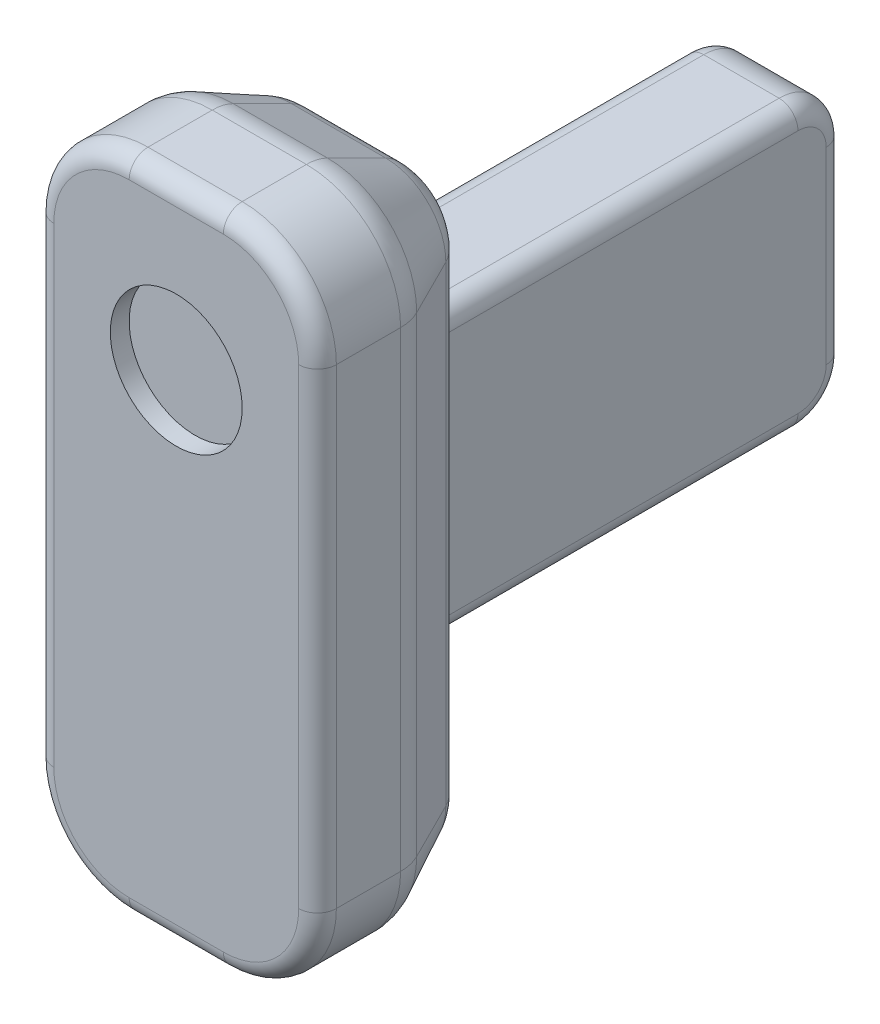
SolidWorks part; units mm, degrees
ref_plane "Front Plane" through (0, 0, 0) normal (0, 0, 1) x (1, 0, 0)
ref_plane "Top Plane" through (0, 0, 0) normal (0, 1, 0) x (1, 0, 0)
ref_plane "Right Plane" through (0, 0, 0) normal (1, 0, 0) x (0, 0, -1)
sketch "Sketch1" plane through (0, 0, 0) normal (0, 0, 1) x (1, 0, 0)
  line L1 (42.3673, -46.3138) -> (72.3673, -46.3138)
  line L2 (42.3673, -46.3138) -> (42.3673, -116.3138)
  line L3 (42.3673, -116.3138) -> (72.3673, -116.3138)
  line L4 (72.3673, -46.3138) -> (72.3673, -116.3138)
  dimension "D1" = 30
  dimension "D2" = 70
extrude "Boss-Extrude1" add sketch "Sketch1" against normal blind 20
fillet "Fillet1" radius 10 4 edges at (42.3673, -46.3138, -10) (72.3673, -46.3138, -10) (42.3673, -116.3138, -10) (72.3673, -116.3138, -10)
fillet "Fillet2" radius 2 8 edges at (69.4383, -113.3848, 0) (57.3673, -116.3138, 0) (45.2962, -113.3848, 0) (42.3673, -81.3138, 0) (45.2962, -49.2427, 0) (57.3673, -46.3138, 0) (69.4383, -49.2427, 0) (72.3673, -81.3138, 0)
chamfer "Chamfer1" distance 5 distance2 10 8 edges at (42.3673, -81.3138, -20) (45.2962, -113.3848, -20) (45.2962, -49.2427, -20) (57.3673, -116.3138, -20) (57.3673, -46.3138, -20) (69.4383, -113.3848, -20) (69.4383, -49.2427, -20) (72.3673, -81.3138, -20) first distance on face at (57.3673, -81.3138, -20)
fillet "Fillet3" radius 5 16 edges at (65.9028, -52.7782, -20) (57.3673, -51.3138, -20) (48.8317, -52.7782, -20) (47.3673, -81.3138, -20) (48.8317, -109.8493, -20) (57.3673, -111.3138, -20) (65.9028, -109.8493, -20) (69.4383, -113.3848, -10) (57.3673, -116.3138, -10) (45.2962, -113.3848, -10) (42.3673, -81.3138, -10) (45.2962, -49.2427, -10) (57.3673, -46.3138, -10) (69.4383, -49.2427, -10) (67.3673, -81.3138, -20) (72.3673, -81.3138, -10)
sketch "Sketch2" plane through (0, 0, -20) normal (0, 0, -1) x (-1, 0, 0)
  line L0 (-64.2771, -81.3138) -> (-50.4574, -81.3138) construction
  line L1 (-64.2771, -56.3138) -> (-64.2771, -106.3138) construction
  line L2 (-50.4574, -106.3138) -> (-50.4574, -56.3138) construction
  line L3 (-57.3673, -108.2236) -> (-57.3673, -54.4039) construction
  line L4 (-62.3673, -108.2236) -> (-52.3673, -108.2236) construction
  line L5 (-52.3673, -54.4039) -> (-62.3673, -54.4039) construction
  line L7 (-63.3673, -96.3138) -> (-51.3673, -96.3138)
  line L8 (-63.3673, -96.3138) -> (-63.3673, -66.3138)
  line L9 (-63.3673, -66.3138) -> (-51.3673, -66.3138)
  line L10 (-51.3673, -96.3138) -> (-51.3673, -66.3138)
  dimension "D1" = 12
  dimension "D2" = 6
  dimension "D3" = 30
  dimension "D4" = 15
extrude "Boss-Extrude2" add sketch "Sketch2" along normal blind 45
fillet "Fillet4" radius 5 2 edges at (57.3673, -66.3138, -65) (57.3673, -96.3138, -65)
sketch "Sketch3" plane through (0, 0, 0) normal (0, 0, 1) x (1, 0, 0)
  line L0 (57.3673, -48.3138) -> (57.3673, -114.3138) construction
  line L1 (62.3673, -48.3138) -> (52.3673, -48.3138) construction
  line L2 (52.3673, -114.3138) -> (62.3673, -114.3138) construction
  line L3 (52.3673, -46.3138) -> (62.3673, -46.3138) construction
  circle A0 centre (57.3673, -63.3138) radius 7
  dimension "D1" = 17
extrude "Cut-Extrude1" cut sketch "Sketch3" against normal blind 2
fillet "Fillet5" radius 2 10 edges at (51.3673, -66.3138, -40) (51.3673, -67.7782, -63.5355) (51.3673, -81.3138, -65) (51.3673, -94.8493, -63.5355) (63.3673, -66.3138, -40) (63.3673, -67.7782, -63.5355) (63.3673, -81.3138, -65) (63.3673, -94.8493, -63.5355) (51.3673, -96.3138, -40) (63.3673, -96.3138, -40)
